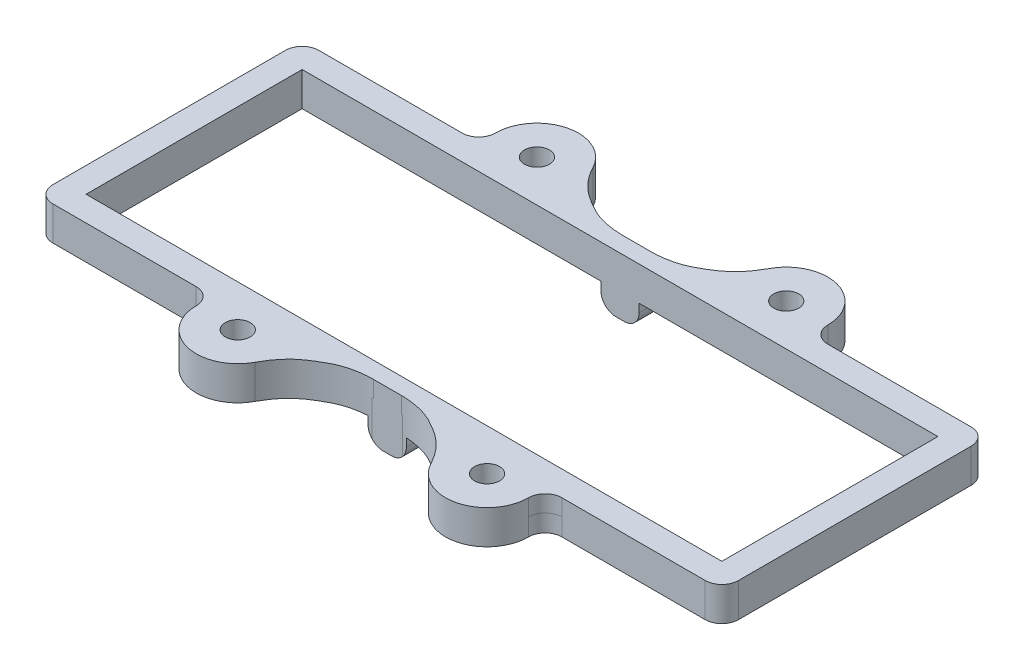
SolidWorks part; units mm, degrees
ref_plane "Front Plane" through (0, 0, 0) normal (0, 0, 1) x (1, 0, 0)
ref_plane "Top Plane" through (0, 0, 0) normal (0, 1, 0) x (1, 0, 0)
ref_plane "Right Plane" through (0, 0, 0) normal (1, 0, 0) x (0, 0, -1)
sketch "Sketch1" plane through (0, 0, 0) normal (0, 1, 0) x (1, 0, 0)
  line L0 (-44.593, 3.4751) -> (37.907, 3.4751) construction
  line L1 (-44.593, 19.4751) -> (37.907, 19.4751)
  line L2 (-44.593, 19.4751) -> (-44.593, -12.5249)
  line L3 (-44.593, -12.5249) -> (37.907, -12.5249)
  line L4 (37.907, 19.4751) -> (37.907, -12.5249)
  line L5 (-41.593, 16.4751) -> (34.907, 16.4751)
  line L6 (-41.593, 16.4751) -> (-41.593, -9.5249)
  line L7 (-41.593, -9.5249) -> (34.907, -9.5249)
  line L8 (34.907, 16.4751) -> (34.907, -9.5249)
  line L9 (-3.343, 19.4751) -> (-3.343, -12.5249) construction
  line L10 (16.657, -12.5249) -> (16.657, -19.5249)
  line L11 (-23.343, 19.4751) -> (16.657, 19.4751)
  line L12 (-23.343, 19.4751) -> (-23.343, 26.4751)
  line L13 (-23.343, 26.4751) -> (16.657, 26.4751)
  line L14 (16.657, 19.4751) -> (16.657, 26.4751)
  line L15 (-23.343, -19.5249) -> (16.657, -19.5249)
  line L16 (-23.343, -12.5249) -> (-23.343, -19.5249)
  line L17 (-23.343, -12.5249) -> (16.657, -12.5249)
  line L18 (-25.2775, 21.4751) -> (22.0201, 21.4751) construction
  circle A0 centre (-18.343, 21.4751) radius 1.5
  circle A1 centre (11.657, 21.4751) radius 1.5
  circle A2 centre (11.657, -14.5249) radius 1.5
  circle A3 centre (-18.343, -14.5249) radius 1.5
  dimension "D1" = 82.5
  dimension "D2" = 32
  dimension "D3" = 76.5
  dimension "D4" = 26
  dimension "D5" = 13
  dimension "D6" = 38.25
  dimension "D7" = 40
  dimension "D8" = 20
  dimension "D9" = 7
  dimension "D10" = 30
  dimension "D12" = 15
  dimension "D13" = 2
extrude "Boss-Extrude1" add sketch "Sketch1" along normal blind 2.085 contours L3 L16 L15 L10 A2 A3 | L4 L1 L2 L3 L5 L8 L7 L6 | L1 L14 L13 L12 A1 A0
sketch "Sketch2" plane through (0, 0, 0) normal (0, -1, 0) x (1, 0, 0)
  line L0 (-3.343, 19.5249) -> (-3.343, -26.4751) construction
  line L1 (-23.343, 19.5249) -> (16.657, 19.5249) construction
  line L2 (-23.343, -26.4751) -> (16.657, -26.4751) construction
  line L3 (-41.593, -3.4751) -> (34.907, -3.4751) construction
  line L4 (-5.843, 19.5249) -> (-0.843, 19.5249)
  line L5 (-5.843, 19.5249) -> (-5.843, 9.5249)
  line L6 (-5.843, 9.5249) -> (-0.843, 9.5249)
  line L7 (-0.843, 19.5249) -> (-0.843, 9.5249)
  line L8 (-41.593, -16.4751) -> (-41.593, 9.5249) construction
  line L9 (34.907, -16.4751) -> (34.907, 9.5249) construction
  line L10 (-0.843, -26.4751) -> (-0.843, -16.4751)
  line L11 (-5.843, -16.4751) -> (-0.843, -16.4751)
  line L12 (-5.843, -26.4751) -> (-5.843, -16.4751)
  line L13 (-5.843, -26.4751) -> (-0.843, -26.4751)
  dimension "D1" = 5
  dimension "D2" = 10
  dimension "D3" = 2.5
extrude "Boss-Extrude2" add sketch "Sketch2" along normal blind 3
fillet "Fillet1" radius 2 4 edges at (-5.843, -3, 14.5249) (-0.843, -3, 14.5249) (-0.843, -3, -21.4751) (-5.843, -3, -21.4751)
fillet "Fillet2" radius 2 4 edges at (-44.593, 1.0425, 12.5249) (-44.593, 1.0425, -19.4751) (37.907, 1.0425, -19.4751) (37.907, 1.0425, 12.5249)
sketch "Sketch3" plane through (0, 0, -26.4751) normal (0, 0, -1) x (-1, 0, 0)
  line L8 (23.343, 0) -> (5.843, 0) construction
  line L9 (6.1655, 0) -> (0.1244, 0)
  line L10 (6.1655, 0) -> (6.1655, -3.3793)
  line L11 (6.1655, -3.3793) -> (0.1244, -3.3793)
  line L12 (0.1244, 0) -> (0.1244, -3.3793)
  line L16 (2.843, -2.8) -> (3.843, -2.8)
  line L17 (5.643, 0.2) -> (23.143, 0.2)
  line L18 (23.143, 0.2) -> (23.143, 1.885)
  line L19 (23.143, 1.885) -> (-16.457, 1.885)
  line L20 (-16.457, 1.885) -> (-16.457, 0.2)
  line L21 (-16.457, 0.2) -> (1.043, 0.2)
  line L22 (2.843, -2.8) -> (3.843, -2.8)
  line L23 (5.643, 0.2) -> (23.143, 0.2)
  line L24 (23.143, 0.2) -> (23.143, 1.885)
  line L25 (23.143, 1.885) -> (-16.457, 1.885)
  line L26 (-16.457, 1.885) -> (-16.457, 0.2)
  line L27 (-16.457, 0.2) -> (1.043, 0.2)
  line L28 (1.043, 0.2) -> (1.043, -1)
  line L29 (1.043, 0.2) -> (1.043, -1)
  line L30 (5.643, -1) -> (5.643, 0.2)
  line L31 (5.643, -1) -> (5.643, 0.2)
  arc A4 (1.043, -1) -> (2.843, -2.8) centre (2.843, -1) ccw
  arc A5 (3.843, -2.8) -> (5.643, -1) centre (3.843, -1) ccw
  arc A6 (1.043, -1) -> (2.843, -2.8) centre (2.843, -1) ccw
  arc A7 (3.843, -2.8) -> (5.643, -1) centre (3.843, -1) ccw
  line M11 (0.843, 0) -> (0.843, -1)
  arc M12 (0.843, -1) -> (2.843, -3) centre (2.843, -1) ccw
  line M13 (2.843, -3) -> (3.843, -3)
  arc M14 (3.843, -3) -> (5.843, -1) centre (3.843, -1) ccw
  line M15 (5.843, -1) -> (5.843, 0)
  dimension "D1" = 0.2
extrude "Cut-Extrude1" cut sketch "Sketch3" against normal through all contours A7 L22 A6 L29 L9 L31 M11 M12 M13 M14 M15
sketch "Sketch4" plane through (0, 2.085, 0) normal (0, 1, 0) x (1, 0, 0)
  line L0 (-3.343, 18.4751) -> (7.657, 18.4751)
  line L1 (7.657, 18.4751) -> (-14.343, 18.4751)
  line L2 (-5.0256, 18.4751) -> (-1.6603, 18.4751)
  line L3 (37.907, 3.4751) -> (-44.593, 3.4751) construction
  line L4 (37.907, 17.4751) -> (37.907, -10.5249) construction
  line L5 (-44.593, 17.4751) -> (-44.593, -10.5249) construction
  line L6 (11.657, 26.4751) -> (11.657, 33.2921)
  line L7 (11.657, 33.2921) -> (-18.343, 33.2921)
  line L8 (-18.343, 33.2921) -> (-18.343, 26.4751)
  line L9 (-18.343, -26.342) -> (-18.343, -19.5249)
  line L10 (11.657, -26.342) -> (-18.343, -26.342)
  line L11 (11.657, -19.5249) -> (11.657, -26.342)
  line L12 (-5.0256, -11.5249) -> (-1.6603, -11.5249)
  line L13 (7.657, -11.5249) -> (-14.343, -11.5249)
  line L14 (-3.343, -11.5249) -> (7.657, -11.5249)
  circle A0 centre (-18.343, 21.4751) radius 5
  circle A1 centre (11.657, 21.4751) radius 5
  circle A2 centre (11.657, -14.5249) radius 5
  circle A3 centre (-18.343, -14.5249) radius 5
  spline S0 degree 3 poles (-13.9208, 23.8084) (-13.3837, 22.8069) (-12.2321, 21.2227) (-10.1423, 19.8877) (-8.5768, 19.0482) (-6.9016, 18.5983) (-5.7419, 18.469) (-5.0256, 18.4751) knots 0 0 0 0 0.314938 0.52444 0.679222 0.802825 1 1 1 1
  spline S1 degree 3 poles (7.2349, 23.8084) (6.6978, 22.8069) (5.5462, 21.2227) (3.4564, 19.8877) (1.8909, 19.0482) (0.2157, 18.5983) (-0.944, 18.469) (-1.6603, 18.4751) knots 0 0 0 0 0.314938 0.52444 0.679222 0.802825 1 1 1 1
  spline S2 degree 3 poles (7.2349, -16.8583) (6.6978, -15.8568) (5.5462, -14.2726) (3.4564, -12.9376) (1.8909, -12.0981) (0.2157, -11.6482) (-0.944, -11.5188) (-1.6603, -11.5249) knots 0 0 0 0 0.314938 0.52444 0.679222 0.802825 1 1 1 1
  spline S3 degree 3 poles (-13.9208, -16.8583) (-13.3837, -15.8568) (-12.2321, -14.2726) (-10.1423, -12.9376) (-8.5768, -12.0981) (-6.9016, -11.6482) (-5.7419, -11.5188) (-5.0256, -11.5249) knots 0 0 0 0 0.314938 0.52444 0.679222 0.802825 1 1 1 1
  line M7 (-23.343, -19.5249) -> (16.657, -19.5249)
  line M15 (16.657, 26.4751) -> (-23.343, 26.4751)
extrude "Cut-Extrude2" cut sketch "Sketch4" against normal through all contours S1 A1 A0 S0 L1 L0 M15 | L7 L8 L6 M15 | S3 A3 A2 S2 L14 L13 L12 M7 | L11 L9 L10 M7
fillet "Fillet3" radius 5 4 edges at (16.657, 1.0425, -26.4751) (-23.343, 1.0425, -26.4751) (-23.343, 1.0425, 19.5249) (16.657, 1.0425, 19.5249)
fillet "Fillet4" radius 2 12 edges at (16.657, 2.085, 13.5249) (-23.343, 0, 13.5249) (-23.343, 0, -20.4751) (16.657, 0, -20.4751) (16.657, 0, 13.5249) (16.657, 2.085, -20.4751) (-23.343, 1.0425, 12.5249) (-23.343, 1.0425, -19.4751) (16.657, 1.0425, -19.4751) (16.657, 1.0425, 12.5249) (-23.343, 2.085, -20.4751) (-23.343, 2.085, 13.5249)
sketch "Sketch5" plane through (0, 2.085, 0) normal (0, 1, 0) x (1, 0, 0)
  line L0 (-23.343, 21.4751) -> (-23.343, 16.4751)
  line L1 (-41.593, 3.4751) -> (34.907, 3.4751) construction
  line L2 (-41.593, 16.4751) -> (-41.593, -9.5249) construction
  line L3 (34.907, 16.4751) -> (34.907, -9.5249) construction
  line L4 (-3.343, -9.5249) -> (-3.343, 43.7071) construction
  line L5 (-41.593, 16.4751) -> (34.907, 16.4751) construction
  line L6 (-3.343, 18.4751) -> (7.657, 18.4751)
  line L7 (7.657, 18.4751) -> (-14.343, 18.4751)
  line L8 (-14.343, 18.4751) -> (-14.343, 31.9361)
  line L9 (-3.343, 18.4751) -> (-3.343, 35.8237) construction
  line L10 (-5.0256, 18.4751) -> (-1.6603, 18.4751)
  line L11 (-41.593, -9.5249) -> (34.907, -9.5249) construction
  line L12 (-23.343, 16.4751) -> (16.657, 16.4751)
  line L13 (16.657, 16.4751) -> (16.657, 21.4751)
  line L14 (16.657, -9.5249) -> (16.657, -14.5249)
  line L15 (-23.343, -9.5249) -> (16.657, -9.5249)
  line L16 (-5.0256, -11.5249) -> (-1.6603, -11.5249)
  line L17 (7.657, -11.5249) -> (-14.343, -11.5249)
  line L18 (-3.343, -11.5249) -> (7.657, -11.5249)
  line L19 (-23.343, -14.5249) -> (-23.343, -9.5249)
  line L21 (34.907, -9.5249) -> (-41.593, -9.5249)
  line L22 (34.907, -9.5249) -> (34.907, 16.4751)
  line L23 (34.907, 16.4751) -> (-41.593, 16.4751)
  line L24 (-41.593, -9.5249) -> (-41.593, 16.4751)
  line L25 (35.907, -12.5249) -> (-42.593, -12.5249)
  line L26 (37.907, -10.5249) -> (37.907, 17.4751)
  line L27 (35.907, 19.4751) -> (-42.593, 19.4751)
  line L28 (-44.593, -10.5249) -> (-44.593, 17.4751)
  circle A0 centre (-18.343, 21.4751) radius 5
  circle A1 centre (11.657, 21.4751) radius 5
  circle A2 centre (11.657, -14.5249) radius 5
  circle A3 centre (-18.343, -14.5249) radius 5
  arc A4 (-42.593, -12.5249) -> (-44.593, -10.5249) centre (-42.593, -10.5249) cw
  arc A5 (-42.593, 19.4751) -> (-44.593, 17.4751) centre (-42.593, 17.4751) ccw
  arc A6 (37.907, 17.4751) -> (35.907, 19.4751) centre (35.907, 17.4751) ccw
  arc A7 (35.907, -12.5249) -> (37.907, -10.5249) centre (35.907, -10.5249) ccw
  spline S0 degree 3 poles (-13.9208, 23.8084) (-13.3837, 22.8069) (-12.2321, 21.2227) (-10.1423, 19.8877) (-8.5768, 19.0482) (-6.9016, 18.5983) (-5.7419, 18.469) (-5.0256, 18.4751) knots 0 0 0 0 0.314938 0.52444 0.679222 0.802825 1 1 1 1
  spline S1 degree 3 poles (7.2349, 23.8084) (6.6978, 22.8069) (5.5462, 21.2227) (3.4564, 19.8877) (1.8909, 19.0482) (0.2157, 18.5983) (-0.944, 18.469) (-1.6603, 18.4751) knots 0 0 0 0 0.314938 0.52444 0.679222 0.802825 1 1 1 1
  spline S2 degree 3 poles (7.2349, -16.8583) (6.6978, -15.8568) (5.5462, -14.2726) (3.4564, -12.9376) (1.8909, -12.0981) (0.2157, -11.6482) (-0.944, -11.5188) (-1.6603, -11.5249) knots 0 0 0 0 0.314938 0.52444 0.679222 0.802825 1 1 1 1
  spline S3 degree 3 poles (-13.9208, -16.8583) (-13.3837, -15.8568) (-12.2321, -14.2726) (-10.1423, -12.9376) (-8.5768, -12.0981) (-6.9016, -11.6482) (-5.7419, -11.5188) (-5.0256, -11.5249) knots 0 0 0 0 0.314938 0.52444 0.679222 0.802825 1 1 1 1
  circle M5 centre (-18.343, 21.4751) radius 1.5
  circle M6 centre (11.657, 21.4751) radius 1.5
  line M7 (-41.593, 16.4751) -> (34.907, 16.4751)
  line M8 (34.907, 16.4751) -> (34.907, -9.5249)
  line M9 (34.907, -9.5249) -> (-41.593, -9.5249)
  line M10 (-41.593, -9.5249) -> (-41.593, 16.4751)
  circle M11 centre (-18.343, -14.5249) radius 1.5
  circle M12 centre (11.657, -14.5249) radius 1.5
  line M13 (35.907, 19.4751) -> (18.657, 19.4751)
  arc M15 (16.657, 21.4751) -> (11.657, 26.4751) centre (11.657, 21.4751) ccw
  arc M16 (11.657, 26.4751) -> (7.2349, 23.8084) centre (11.657, 21.4751) ccw
  spline M17 degree 3 poles (7.2349, 23.8084) (6.6978, 22.8069) (5.5462, 21.2227) (3.4564, 19.8877) (1.8909, 19.0482) (0.2157, 18.5983) (-0.944, 18.469) (-1.6603, 18.4751) knots 0 0 0 0 0.314938 0.52444 0.679222 0.802825 1 1 1 1 only from (7.2349, 23.8084) to (-1.5064, 18.4751)
  line M18 (-1.5064, 18.4751) -> (-5.1795, 18.4751)
  spline M19 degree 3 poles (-5.0256, 18.4751) (-5.7419, 18.469) (-6.9016, 18.5983) (-8.5768, 19.0482) (-10.1423, 19.8877) (-12.2321, 21.2227) (-13.3837, 22.8069) (-13.9208, 23.8084) knots 0 0 0 0 0.197175 0.320778 0.47556 0.685062 1 1 1 1 only from (-5.1795, 18.4751) to (-13.9208, 23.8084)
  arc M20 (-13.9208, 23.8084) -> (-18.343, 26.4751) centre (-18.343, 21.4751) ccw
  arc M21 (-18.343, 26.4751) -> (-23.343, 21.4751) centre (-18.343, 21.4751) ccw
  line M23 (-25.343, 19.4751) -> (-42.593, 19.4751)
  arc M24 (-42.593, 19.4751) -> (-44.593, 17.4751) centre (-42.593, 17.4751) ccw
  line M25 (-44.593, 17.4751) -> (-44.593, -10.5249)
  arc M26 (-44.593, -10.5249) -> (-42.593, -12.5249) centre (-42.593, -10.5249) ccw
  line M27 (-42.593, -12.5249) -> (-25.343, -12.5249)
  arc M29 (-23.343, -14.5249) -> (-18.343, -19.5249) centre (-18.343, -14.5249) ccw
  arc M30 (-18.343, -19.5249) -> (-13.9208, -16.8583) centre (-18.343, -14.5249) ccw
  spline M31 degree 3 poles (-13.9208, -16.8583) (-13.3837, -15.8568) (-12.2321, -14.2726) (-10.1423, -12.9376) (-8.5768, -12.0981) (-6.9016, -11.6482) (-5.7419, -11.5188) (-5.0256, -11.5249) knots 0 0 0 0 0.314938 0.52444 0.679222 0.802825 1 1 1 1 only from (-13.9208, -16.8583) to (-5.1795, -11.5249)
  line M32 (-5.1795, -11.5249) -> (-1.5064, -11.5249)
  spline M33 degree 3 poles (-1.6603, -11.5249) (-0.944, -11.5188) (0.2157, -11.6482) (1.8909, -12.0981) (3.4564, -12.9376) (5.5462, -14.2726) (6.6978, -15.8568) (7.2349, -16.8583) knots 0 0 0 0 0.197175 0.320778 0.47556 0.685062 1 1 1 1 only from (-1.5064, -11.5249) to (7.2349, -16.8583)
  arc M34 (7.2349, -16.8583) -> (11.657, -19.5249) centre (11.657, -14.5249) ccw
  arc M35 (11.657, -19.5249) -> (16.657, -14.5249) centre (11.657, -14.5249) ccw
  line M37 (18.657, -12.5249) -> (35.907, -12.5249)
  arc M38 (35.907, -12.5249) -> (37.907, -10.5249) centre (35.907, -10.5249) ccw
  line M39 (37.907, -10.5249) -> (37.907, 17.4751)
  arc M40 (37.907, 17.4751) -> (35.907, 19.4751) centre (35.907, 17.4751) ccw
  dimension "D1" = 2
extrude "Boss-Extrude3" add sketch "Sketch5" along normal blind 2 contours A0 L8 M20 M21 M5 | L6 S1 L7 S0 A0 L12 A1 M18 | A0 L0 M7 | L8 A0 M20 | A0 L7 M19 | A1 L6 M17 | A1 M15 M16 M6 | A1 L13 M7 | L19 A3 M9 | A3 M29 M30 M11 | L17 S3 S2 A2 L15 A3 M32 | L17 A3 M31 | A2 L17 M33 | A2 M34 M35 M12 | A2 L14 M9 | L27 L13 L14 L25 M13 M7 M8 M9 M37 M38 M39 M40 | L0 L27 L25 L19 M23 M24 M25 M26 M27 M9 M10 M7 | A2 L25 | A2 L25 M33 | A3 L25 | L25 A3 M31 | A1 L27 | A1 L27 M17 | A0 L8 L27 | A0 L27 M19 | L8 A0 L27
fillet "Fillet5" radius 2 12 edges at (16.2396, 3.085, 12.5249) (17.4483, 2.085, -19.4751) (16.5516, 2.085, -20.4535) (16.2396, 3.085, -19.4751) (-23.2375, 2.085, -20.4535) (-24.1342, 2.085, -19.4751) (-22.9255, 3.085, -19.4751) (-24.1342, 2.085, 12.5249) (-22.9255, 3.085, 12.5249) (-23.2375, 2.085, 13.5034) (17.4483, 2.085, 12.5249) (16.5516, 2.085, 13.5034)
